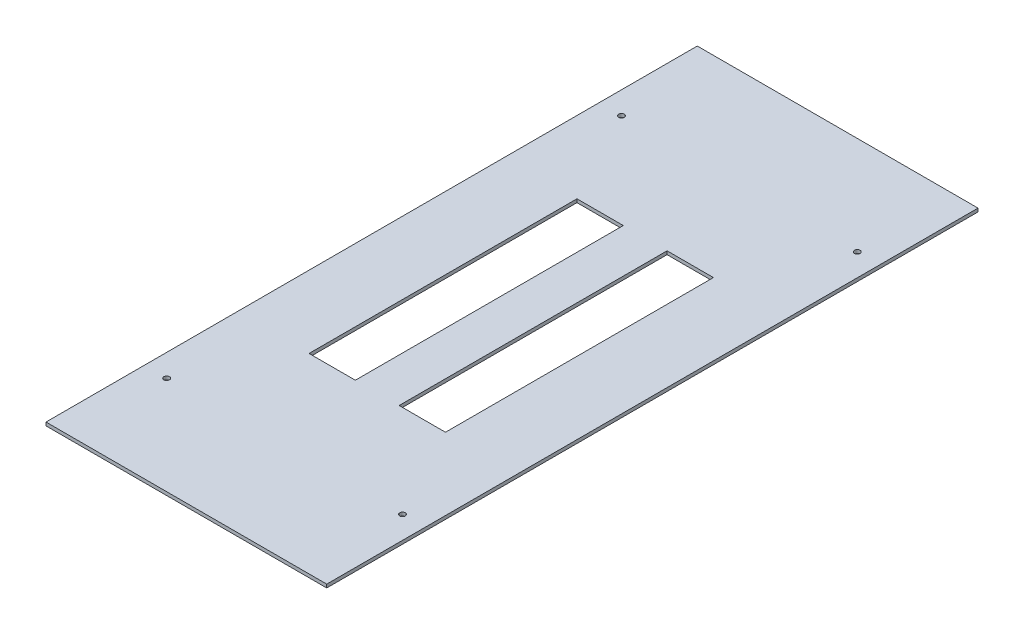
SolidWorks part; units mm, degrees
material "6061 Alloy"
ref_plane "Front Plane" through (0, 0, 0) normal (0, 0, 1) x (1, 0, 0)
ref_plane "Top Plane" through (0, 0, 0) normal (0, 1, 0) x (1, 0, 0)
ref_plane "Right Plane" through (0, 0, 0) normal (1, 0, 0) x (0, 0, -1)
sketch "Sketch1" plane through (0, 0, 0) normal (0, 1, 0) x (1, 0, 0)
  line L0 (0, 212.5) -> (0, -212.5) construction
  line L1 (-115, 212.5) -> (115, 212.5)
  line L2 (-115, 212.5) -> (-115, -212.5)
  line L3 (-115, -212.5) -> (115, -212.5)
  line L4 (115, 212.5) -> (115, -212.5)
  line L5 (-115, 212.5) -> (115, -212.5) construction
  line L6 (-115, -212.5) -> (115, 212.5) construction
  line L8 (-115, 0) -> (115, 0) construction
  point P0 (0, 0)
  point P8 (-105, 202.5)
  point P14 (105, 202.5)
  point P16 (105, -202.5)
  point P17 (-105, -202.5)
  dimension "D1" = 210
  dimension "D2" = 405
  dimension "D3" = 10
  dimension "D4" = 10
extrude "Boss-Extrude1" add sketch "Sketch1" against normal blind 3 contours L1 L4 L3 L2
hole_wizard "Ø5.0 (4) Diameter Hole1" positions "Sketch2" profile "Sketch4" hole size "Ø5.0" standard "ANSI Metric" end condition through all
sketch "Sketch2" plane through (0, 0, 0) normal (0, 1, 0) x (1, 0, 0)
  point P0 (-105, 202.5)
  point P3 (105, 202.5)
  point P6 (105, -202.5)
  point P9 (-105, -202.5)
sketch "Sketch4" plane through (-105, 0, -202.5) normal (1, 0, 0) x (0, 0, 1)
  line L0 (0, 0) -> (0, 3)
  line L1 (0, 3) -> (2.5, 3)
  line L2 (2.5, 3) -> (2.5, 0)
  line L5 (2.5, 0) -> (0, 0)
  line L11 (0, -6.35) -> (0, 107.95) construction
  dimension "Thru Hole Dia." = 5
  dimension "Thru Hole Depth" = 3
sketch "Sketch5" plane through (0, 0, 0) normal (0, 1, 0) x (1, 0, 0)
  line L0 (0, 212.5) -> (0, -212.5) construction
  line L1 (-55.75, 113.6) -> (-24.5, 113.6) construction
  line L2 (-55.75, 113.6) -> (-55.75, -115) construction
  line L3 (-55.75, -115) -> (-24.5, -115) construction
  line L4 (-24.5, 113.6) -> (-24.5, -115) construction
  line L5 (24.5, 113.6) -> (24.5, -115) construction
  line L6 (-60.75, 118.6) -> (-19.5, 118.6)
  line L7 (-60.75, 118.6) -> (-60.75, -120)
  line L8 (-60.75, -120) -> (-19.5, -120)
  line L9 (-19.5, 118.6) -> (-19.5, -120)
  line L10 (55.75, -115) -> (24.5, -115) construction
  line L11 (55.75, 113.6) -> (55.75, -115) construction
  line L12 (55.75, 113.6) -> (24.5, 113.6) construction
  line L13 (19.5, 118.6) -> (19.5, -120)
  line L14 (60.75, -120) -> (19.5, -120)
  line L15 (60.75, 118.6) -> (60.75, -120)
  line L16 (60.75, 118.6) -> (19.5, 118.6)
  dimension "D1" = 88.9
  dimension "D2" = 228.6
  dimension "D3" = 55.75
  dimension "D4" = 5
  dimension "D5" = 5
  dimension "D6" = 5
  dimension "D7" = 5
  dimension "D8" = 24.5
extrude "Cut-Extrude1" cut sketch "Sketch5" against normal through all
sketch "Sketch6" plane through (0, 0, 0) normal (0, 1, 0) x (1, 0, 0)
  line L1 (-115, -212.5) -> (115, -212.5)
  line L2 (-115, -212.5) -> (-115, 212.5)
  line L3 (-115, 212.5) -> (115, 212.5)
  line L4 (115, -212.5) -> (115, 212.5)
  line L5 (-115, -212.5) -> (115, 212.5) construction
  line L6 (-115, 212.5) -> (115, -212.5) construction
  line L7 (-125, -290) -> (125, -290)
  line L8 (-125, -290) -> (-125, 290)
  line L9 (-125, 290) -> (125, 290)
  line L10 (125, -290) -> (125, 290)
  line L11 (-125, -290) -> (125, 290) construction
  line L12 (-125, 290) -> (125, -290) construction
  point P0 (0, 0)
  point P7 (0, 0)
  dimension "D1" = 250
  dimension "D2" = 580
extrude "Boss-Extrude3" add sketch "Sketch6" against normal up to surface (3 mm away) up to face at (-40.125, -3, 0.7)
